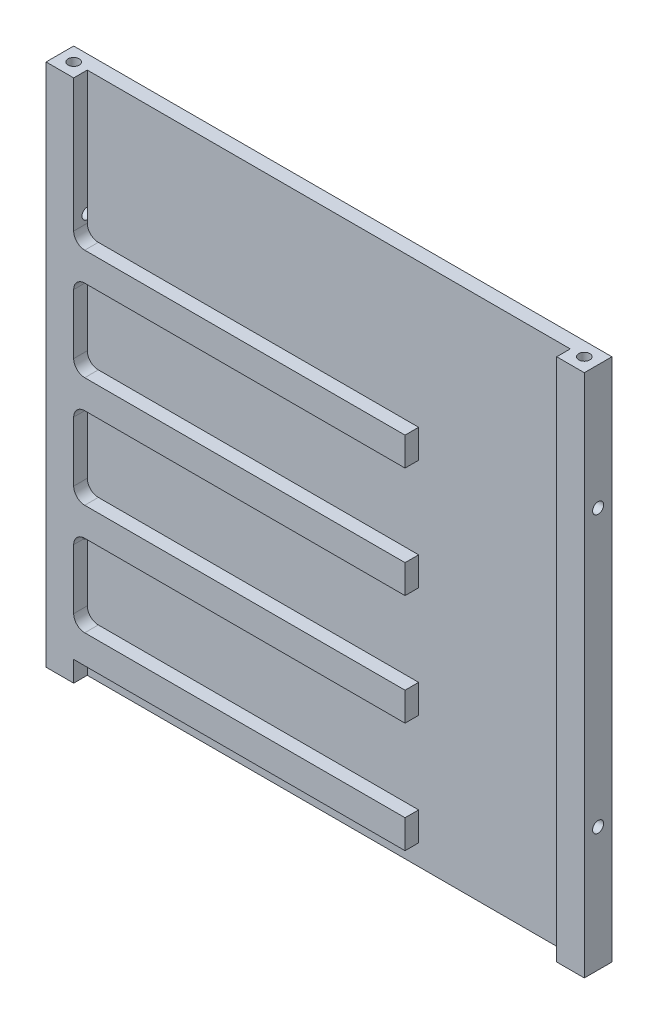
SolidWorks part; units mm, degrees
note: The reader was unsure of these and kept them because the rebuilt part matched: shared geometry of "Sketch3<5>".
material "6061 Alloy"
ref_plane "Front Plane" through (0, 0, 0) normal (0, 0, 1) x (1, 0, 0)
ref_plane "Top Plane" through (0, 0, 0) normal (0, 1, 0) x (1, 0, 0)
ref_plane "Right Plane" through (0, 0, 0) normal (1, 0, 0) x (0, 0, -1)
sketch "Sketch1" plane through (0, 0, 0) normal (0, 0, 1) x (1, 0, 0)
  line L1 (0, 0) -> (97.46, 0)
  line L2 (0, 0) -> (0, 97.46)
  line L3 (0, 97.46) -> (97.46, 97.46)
  line L4 (97.46, 0) -> (97.46, 97.46)
extrude "Boss-Extrude1" add sketch "Sketch1" along normal blind 1.27 contours L2 L3 L4 L1
sketch "Sketch3" plane through (0, 0, 1.27) normal (0, 0, 1) x (1, 0, 0)
  line L0 (0, 0) -> (0, 5) construction
  line L1 (0, 5) -> (65, 5)
  line L2 (65, 5) -> (65, 10.1725)
  line L3 (65, 10.1725) -> (0, 10.1725)
  line L4 (0, 25) -> (65, 25)
  line L5 (65, 25) -> (65, 30.1725)
  line L6 (65, 30.1725) -> (0, 30.1725)
  line L7 (0, 65) -> (0, 70.1725)
  line L8 (0, 45) -> (65, 45)
  line L9 (65, 45) -> (65, 50.1725)
  line L10 (65, 50.1725) -> (0, 50.1725)
  line L11 (0, 50.1725) -> (0, 45)
  line L12 (0, 65) -> (65, 65)
  line L13 (65, 65) -> (65, 70.1725)
  line L14 (65, 70.1725) -> (0, 70.1725)
  line L15 (0, 0) -> (5, 0)
  line L16 (0, 5) -> (0, 10.1725)
  line L17 (0, 25) -> (0, 30.1725)
  line L18 (0, 20) -> (0, 25) construction
  line L19 (0, 40) -> (0, 45) construction
  line L20 (0, 60) -> (0, 65) construction
  line L21 (5, 0) -> (5, 97.46)
  line L22 (5, 97.46) -> (0, 97.46)
  line L23 (0, 97.46) -> (0, 0)
  line L24 (97.46, 0) -> (92.46, 0)
  line L25 (97.46, 0) -> (97.46, 97.46)
  line L26 (97.46, 97.46) -> (92.46, 97.46)
  line L27 (92.46, 97.46) -> (92.46, 0)
  line L28 (0, 97.46) -> (0, 92.46)
  line L29 (92.46, 97.46) -> (92.46, 92.46)
  line L30 (92.46, 5) -> (92.46, 0)
  line L31 (92.46, 5) -> (97.46, 5)
  line L32 (92.46, 92.46) -> (97.46, 92.46)
  line L33 (0, 92.46) -> (5, 92.46)
  line L34 (5, 0) -> (92.46, 0)
  line L35 (92.46, 97.46) -> (5, 97.46)
  point P8 (97.46, 0)
  line M4 (0, 0) -> (97.46, 0)
  line M5 (97.46, 0) -> (97.46, 97.46)
  line M6 (97.46, 97.46) -> (0, 97.46)
  line M7 (0, 97.46) -> (0, 0)
  dimension "D1" = 4
extrude "Boss-Extrude2" add sketch "Sketch3" along normal blind 3.73 contours L14 L21 M6 M7 | L12 L21 L14 M7 | L10 L21 L12 M7 | L8 L21 L10 M7 | L6 L21 L8 M7 | L4 L21 L6 M7 | L3 L21 L4 M7 | L27 M6 M4 M5 | L1 L21 L3 M7 | L21 L1 L2 L3 | L21 L4 L5 L6 | L21 L8 L9 L10 | L21 L12 L13 L14
sketch "Sketch4" plane through (0, 0, 0) normal (0, -1, 0) x (1, 0, 0)
  line L0 (97.46, 0) -> (94.96, 0) construction
  line L1 (97.46, 0) -> (97.46, 2.5)
  circle A0 centre (94.96, 2.5) radius 1
sketch "Sketch5" plane through (0, 0, 0) normal (0, -1, 0) x (1, 0, 0)
  circle A0 centre (2.5, 2.5) radius 1
sketch "Sketch6" plane through (0, 97.46, 0) normal (0, 1, 0) x (-1, 0, 0)
  line L0 (-97.46, 0) -> (-94.96, 0) construction
  line L1 (-94.96, 0) -> (-94.96, 2.5) construction
  circle A0 centre (-94.96, 2.5) radius 1
sketch "Sketch7" plane through (0, 97.46, 0) normal (0, 1, 0) x (-1, 0, 0)
  circle A0 centre (-2.5, 2.5) radius 1
extrude "Cut-Extrude2" cut sketch "Sketch7" against normal blind 5
extrude "Cut-Extrude3" cut sketch "Sketch6" against normal blind 5 contours A0
extrude "Cut-Extrude4" cut sketch "Sketch4" against normal blind 5 contours A0
extrude "Cut-Extrude5" cut sketch "Sketch5" against normal blind 5 contours A0
fillet "Fillet1" radius 2 7 edges at (5, 70.1725, 3.135) (5, 65, 3.135) (5, 50.1725, 3.135) (5, 45, 3.135) (5, 30.1725, 3.135) (5, 10.1725, 3.135) (5, 25, 3.135)
sketch "Sketch8" plane through (0, 0, 0) normal (-1, 0, 0) x (0, 0, 1)
  line L4 (0, 97.46) -> (0, 0) construction
  line L5 (0, 48.73) -> (2.5, 48.73) construction
  line L6 (2.5, 23.73) -> (2.5, 73.73) construction
  circle A2 centre (2.5, 23.73) radius 1
  circle A3 centre (2.5, 73.73) radius 1
extrude "Cut-Extrude6" cut sketch "Sketch8" against normal blind 10
sketch "Sketch9" plane through (97.46, 0, 0) normal (1, 0, 0) x (0, 0, -1)
  line L0 (0, 0) -> (0, 97.46) construction
  line L1 (0, 48.73) -> (-2.5, 48.73) construction
  line L2 (-2.5, 73.73) -> (-2.5, 23.73) construction
  circle A0 centre (-2.5, 73.73) radius 1
  circle A1 centre (-2.5, 23.73) radius 1
extrude "Cut-Extrude7" cut sketch "Sketch9" against normal blind 10
extrude "Boss-Extrude3" add sketch "Sketch3<5>" along normal blind 1.27 contours L27 L21 L14 L13 L12 L10 L9 L8 L6 L5 L4 L3 L2 L1 M6 M4
sketch "Sketch3<5>" plane through (0, 0, 1.27) normal (0, 0, 1) x (1, 0, 0) same geometry as "Sketch3"
sketch "Sketch10" plane through (0, 0, 0) normal (0, -1, 0) x (1, 0, 0)
  line L0 (5, 5) -> (0, 5)
  line L1 (0, 5) -> (0, 0)
  line L2 (0, 0) -> (97.46, 0)
  line L3 (97.46, 0) -> (97.46, 5)
  line L4 (97.46, 5) -> (92.46, 5)
  line L5 (92.46, 5) -> (92.46, 2.54)
  line L6 (92.46, 2.54) -> (5, 2.54)
  line L7 (5, 2.54) -> (5, 5)
extrude "Cut-Extrude8" cut sketch "Sketch10" against normal blind 1.27
sketch "Sketch11" plane through (0, 97.46, 0) normal (0, 1, 0) x (1, 0, 0)
  line L0 (92.46, -2.54) -> (92.46, -5)
  line L1 (92.46, -5) -> (97.46, -5)
  line L2 (97.46, -5) -> (97.46, 0)
  line L3 (97.46, 0) -> (0, 0)
  line L4 (0, 0) -> (0, -5)
  line L5 (0, -5) -> (5, -5)
  line L6 (5, -5) -> (5, -2.54)
  line L7 (5, -2.54) -> (92.46, -2.54)
extrude "Cut-Extrude9" cut sketch "Sketch11" against normal blind 1.27
